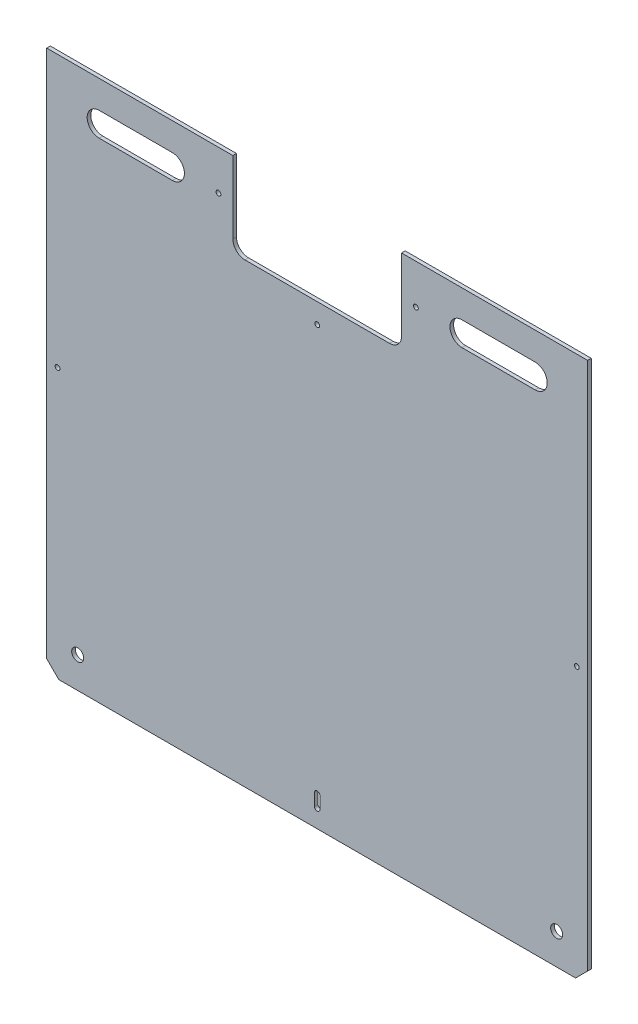
SolidWorks part; units mm, degrees
ref_plane "Piano frontale" through (0, 0, 0) normal (0, 0, 1) x (1, 0, 0)
ref_plane "Piano superiore" through (0, 0, 0) normal (0, 1, 0) x (1, 0, 0)
ref_plane "Piano destro" through (0, 0, 0) normal (1, 0, 0) x (0, 0, -1)
sketch "Schizzo1" plane through (0, 0, 0) normal (0, 0, 1) x (1, 0, 0)
  line L0 (0, 10) -> (0, 449)
  line L1 (0, 449) -> (154.5, 449)
  line L2 (449, 449) -> (449, 10)
  line L3 (439, 0) -> (10, 0)
  line L4 (154.5, 449) -> (154.5, 389)
  line L5 (164.5, 379) -> (284.5, 379)
  line L6 (294.5, 389) -> (294.5, 449)
  line L7 (294.5, 449) -> (449, 449)
  line L8 (154.5, 415.9998) -> (294.5, 415.9998) construction
  line L9 (224.5, 379) -> (224.5, 419) construction
  line L10 (344.7159, 415.9998) -> (405.4404, 415.9998) construction
  line L11 (344.7159, 425.9998) -> (405.4404, 425.9998)
  line L12 (344.7159, 405.9998) -> (405.4404, 405.9998)
  line L13 (104.2841, 415.9998) -> (43.5596, 415.9998) construction
  line L14 (104.2841, 425.9998) -> (43.5596, 425.9998)
  line L15 (104.2841, 405.9998) -> (43.5596, 405.9998)
  line L16 (0, 0) -> (224.5, 224.5) construction
  line L17 (224.5, 224.5) -> (449, 0) construction
  line L18 (224.5, 15) -> (224.5, 25) construction
  line L19 (222.25, 15) -> (222.25, 25)
  line L20 (226.75, 15) -> (226.75, 25)
  line L21 (10, 0) -> (0, 10)
  line L22 (449, 10) -> (439, 0)
  arc A0 (154.5, 389) -> (164.5, 379) centre (164.5, 389) ccw
  arc A1 (294.5, 389) -> (284.5, 379) centre (284.5, 389) cw
  circle A2 centre (142.5666, 415.9998) radius 2
  circle A3 centre (224.5, 362.449) radius 2
  circle A4 centre (306.4334, 415.9998) radius 2
  circle A5 centre (9, 223.8264) radius 2
  circle A6 centre (440, 224.5) radius 2
  arc A8 (344.7159, 425.9998) -> (344.7159, 405.9998) centre (344.7159, 415.9998) ccw
  arc A9 (405.4404, 405.9998) -> (405.4404, 425.9998) centre (405.4404, 415.9998) ccw
  arc A10 (104.2841, 425.9998) -> (104.2841, 405.9998) centre (104.2841, 415.9998) cw
  arc A11 (43.5596, 405.9998) -> (43.5596, 425.9998) centre (43.5596, 415.9998) cw
  circle A12 centre (25.7025, 25.7025) radius 5
  circle A13 centre (423.2975, 25.7025) radius 5
  arc A14 (222.25, 15) -> (226.75, 15) centre (224.5, 15) ccw
  arc A15 (226.75, 25) -> (222.25, 25) centre (224.5, 25) ccw
  point P11 (154.5, 379)
  point P14 (294.5, 379)
  point P33 (375.0781, 415.9998)
  point P40 (73.9219, 415.9998)
  point P52 (224.5, 20)
  dimension "D5" = 10
  dimension "D6" = 4
  dimension "D7" = 4
  dimension "D8" = 4
  dimension "D9" = 4
  dimension "D12" = 10
  dimension "D1" = 449
  dimension "D2" = 449
  dimension "D3" = 140
  dimension "D4" = 70
  dimension "D11" = 20
  dimension "D13" = 9
  dimension "D14" = 9
  dimension "D15" = 4.5
  dimension "D16" = 10
  dimension "D17" = 15
extrude "Estrusione-Estrusione1" add sketch "Schizzo1" along normal blind 3
